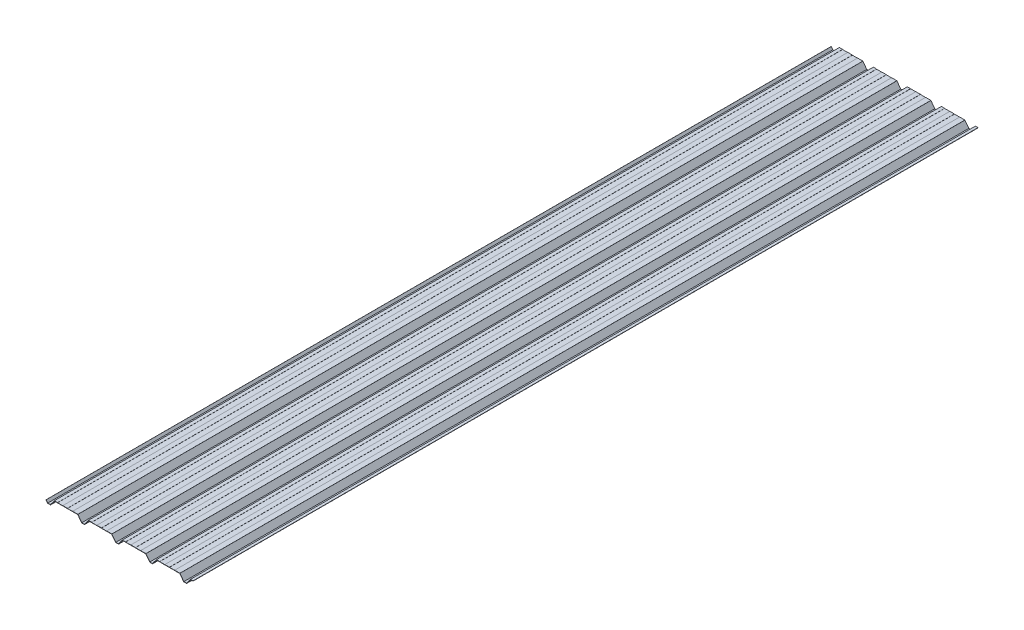
SolidWorks part; units mm, degrees
material "Ductile Iron (SN)"
ref_plane "Front Plane" through (0, 0, 0) normal (0, 0, 1) x (1, 0, 0)
ref_plane "Top Plane" through (0, 0, 0) normal (0, 1, 0) x (1, 0, 0)
ref_plane "Right Plane" through (0, 0, 0) normal (1, 0, 0) x (0, 0, -1)
sketch "Sketch1" plane through (0, 0, 0) normal (0, 0, 1) x (1, 0, 0)
  line L0 (-20, 0) -> (0, 0)
  line L1 (-20, 0) -> (-50, -40)
  line L2 (-50, -40) -> (-70, -40)
  line L3 (-70, -40) -> (-100, 0)
  line L4 (-100, 0) -> (-280, 0)
  line L5 (-280, 0) -> (-310, -40)
  line L6 (-310, -40) -> (-330, -40)
  line L7 (-330, -40) -> (-360, 0)
  line L8 (-360, 0) -> (-540, 0)
  line L9 (-540, 0) -> (-570, -40)
  line L10 (-570, -40) -> (-590, -40)
  line L11 (-590, -40) -> (-620, 0)
  line L12 (-620, 0) -> (-800, 0)
  line L13 (-800, 0) -> (-830, -40)
  line L14 (-830, -40) -> (-850, -40)
  line L15 (-850, -40) -> (-880, 0)
  line L16 (-880, 0) -> (-1060, 0)
  line L17 (-1060, 0) -> (-1090, -40)
  line L18 (-1090, -40) -> (-1110, -40)
  line L19 (-1110, -40) -> (-1122, -24)
  line L20 (-1111, -42) -> (-1123.6, -25.2)
  line L21 (-1089, -42) -> (-1111, -42)
  line L22 (-1059, -2) -> (-1089, -42)
  line L23 (-881, -2) -> (-1059, -2)
  line L24 (-851, -42) -> (-881, -2)
  line L25 (-829, -42) -> (-851, -42)
  line L26 (-799, -2) -> (-829, -42)
  line L27 (-621, -2) -> (-799, -2)
  line L28 (-591, -42) -> (-621, -2)
  line L29 (-569, -42) -> (-591, -42)
  line L30 (-539, -2) -> (-569, -42)
  line L31 (-361, -2) -> (-539, -2)
  line L32 (-331, -42) -> (-361, -2)
  line L33 (-309, -42) -> (-331, -42)
  line L34 (-279, -2) -> (-309, -42)
  line L35 (-101, -2) -> (-279, -2)
  line L36 (-71, -42) -> (-101, -2)
  line L37 (-49, -42) -> (-71, -42)
  line L38 (-19, -2) -> (-49, -42)
  line L39 (-19, -2) -> (0, -2)
  line L40 (0, 0) -> (0, -2)
  line L41 (-1122, -24) -> (-1123.6, -25.2)
  dimension "D1" = 180
  dimension "D2" = 20
  dimension "D3" = 30
  dimension "D4" = 40
  dimension "D5" = 20
  dimension "D6" = 20
  dimension "D7" = 180
  dimension "D8" = 2
extrude "Boss-Extrude1" add sketch "Sketch1" against normal blind 6000
sketch "Sketch2" plane through (0, 0, 0) normal (0, 1, 0) x (1, 0, 0)
  line L0 (-100, 6000) -> (-280, 6000) construction
  line L1 (-100, 0) -> (-140, 0)
  line L2 (-100, 0) -> (-100, 6000)
  line L3 (-100, 6000) -> (-140, 6000)
  line L4 (-140, 0) -> (-140, 6000)
  line L6 (-140, 0) -> (-180, 0)
  line L7 (-140, 0) -> (-140, 6000)
  line L8 (-140, 6000) -> (-180, 6000)
  line L9 (-180, 0) -> (-180, 6000)
  line L10 (-180, 0) -> (-215, 0)
  line L11 (-180, 0) -> (-180, 6000)
  line L12 (-180, 6000) -> (-215, 6000)
  line L13 (-215, 0) -> (-215, 6000)
  line L14 (-215, 0) -> (-255, 0)
  line L15 (-215, 0) -> (-215, 6000)
  line L16 (-215, 6000) -> (-255, 6000)
  line L17 (-255, 0) -> (-255, 6000)
  line L18 (-255, 0) -> (-280, 0)
  line L19 (-255, 0) -> (-255, 6000)
  line L20 (-255, 6000) -> (-280, 6000)
  line L21 (-280, 0) -> (-280, 6000)
  dimension "D1" = 40
  dimension "D2" = 40
  dimension "D3" = 35
  dimension "D4" = 40
extrude "Cut-Extrude1" cut sketch "Sketch2" against normal blind 0.5 contours L9 L6 L4 L8 | L17 L14 L13 L16 region at (-160, 0, -3000) region at (-235, 0, -3000)
extrude "Boss-Extrude3" add sketch "Sketch2<9>" along normal blind 0.5 contours L4 L1 L2 L3 | L13 L10 L9 L12 | L21 L18 L17 L20 region at (-120, 0, -3000) region at (-197.5, 0, -3000) region at (-267.5, 0, -3000)
sketch "Sketch2<9>" plane through (0, 0, 0) normal (0, 1, 0) x (1, 0, 0) same geometry as "Sketch2"
pattern_linear "LPattern1" count 4 spacing 260 along (-1, 0, 0) of "Cut-Extrude1", "Boss-Extrude3"
